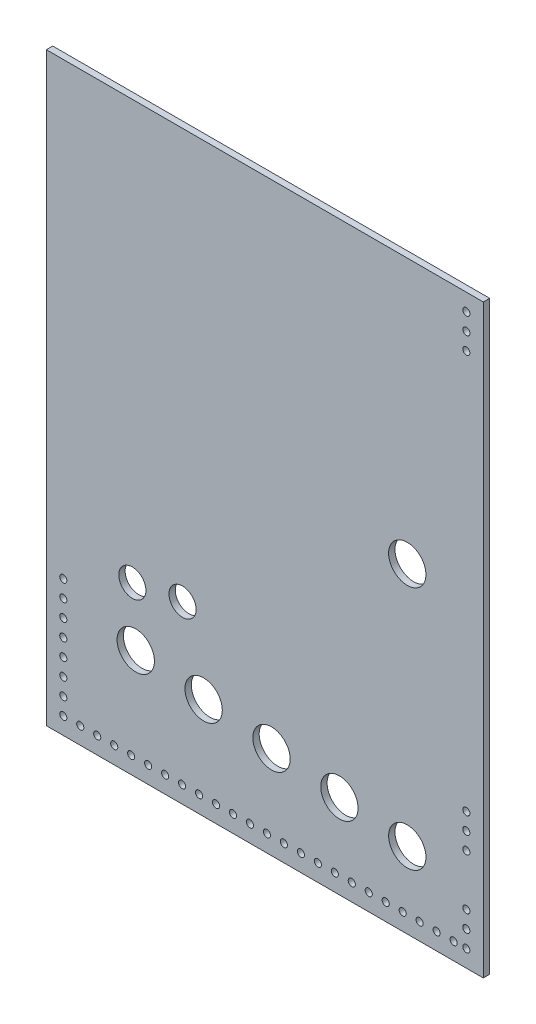
SolidWorks part; units mm, degrees
material "Polypropylene"
ref_plane "Front Plane" through (0, 0, 0) normal (0, 0, 1) x (1, 0, 0)
ref_plane "Top Plane" through (0, 0, 0) normal (0, 1, 0) x (1, 0, 0)
ref_plane "Right Plane" through (0, 0, 0) normal (1, 0, 0) x (0, 0, -1)
sketch "Sketch1" plane through (0, 0, 0) normal (0, 0, 1) x (1, 0, 0)
  line L0 (270.1144, -382.3444) -> (270.1144, -198.1944) construction
  line L1 (0, 0) -> (327.025, 0)
  line L2 (0, 0) -> (0, -438.15)
  line L3 (0, -438.15) -> (327.025, -438.15)
  line L4 (327.025, 0) -> (327.025, -438.15)
  circle A4 centre (270.1144, -198.1944) radius 13.97
  circle A5 centre (101.9257, -306.8134) radius 10.16
  circle A6 centre (64.3744, -313.2564) radius 10.16
  dimension "D4" = 27.94
  dimension "D5" = 20.32
  dimension "D6" = 20.32
  dimension "D1" = 438.15
  dimension "D2" = 327.025
  dimension "D3" = 184.15
extrude "Boss-Extrude1" add sketch "Sketch1" along normal blind 4.7625
sketch "Sketch2" plane through (0, 0, 4.7625) normal (0, 0, 1) x (1, 0, 0)
  circle A1 centre (66.9144, -355.9045) radius 13.97
  dimension "D1" = 27.94
extrude "Cut-Extrude1" cut sketch "Sketch2" against normal up to surface (4.7625 mm away) up to face at (163.5125, -219.075, 0)
sketch "Sketch3" plane through (0, 0, 4.7625) normal (0, 0, 1) x (1, 0, 0)
  line L0 (66.9144, -355.9045) -> (327.025, -355.9045) construction
  line L1 (327.025, -438.15) -> (327.025, 0) construction
  line L2 (66.9144, -355.9045) -> (117.7144, -355.9045) construction
  line L3 (117.7144, -355.9045) -> (168.5144, -355.9045) construction
  line L4 (168.5144, -355.9045) -> (219.3144, -355.9045) construction
  line L5 (219.3144, -355.9045) -> (270.1144, -355.9045) construction
  line L6 (117.7144, -355.9045) -> (117.7144, -362.2545) construction
  line L7 (168.5144, -355.9045) -> (168.5144, -368.6045) construction
  line L8 (219.3144, -355.9045) -> (219.3144, -374.9545) construction
  line L9 (270.1144, -355.9045) -> (270.1144, -381.3045) construction
  line L10 (117.7144, -355.9045) -> (117.7144, -362.2545) construction
  circle A0 centre (117.7144, -362.2545) radius 13.97
  circle A1 centre (168.5144, -368.6045) radius 13.97
  circle A2 centre (219.3144, -374.9545) radius 13.97
  circle A3 centre (270.1144, -381.3045) radius 13.97
  dimension "D8" = 27.94
  dimension "D9" = 27.94
  dimension "D10" = 27.94
  dimension "D11" = 27.94
  dimension "D1" = 50.8
  dimension "D2" = 50.8
  dimension "D3" = 50.8
  dimension "D4" = 50.8
  dimension "D5" = 12.7
  dimension "D6" = 19.05
  dimension "D7" = 25.4
  dimension "D12" = 6.35
extrude "Cut-Extrude2" cut sketch "Sketch3" against normal up to surface (4.7625 mm away) contours A0 | A1 | A2 | A3 up to face at (80.8844, -355.9045, 0)
sketch "Sketch4" plane through (0, 0, 0) normal (0, 0, -1) x (-1, 0, 0)
  line L0 (-12.7, -438.15) -> (-12.7, -425.45) construction
  line L1 (0, -438.15) -> (-327.025, -438.15) construction
  line L2 (-12.7, -425.45) -> (0, -425.45) construction
  line L3 (0, 0) -> (0, -438.15) construction
  line L4 (-327.025, -425.45) -> (0, -425.45) construction
  line L5 (-327.025, 0) -> (0, 0) construction
  line L6 (-163.5125, 0) -> (-163.5125, -438.15) construction
  line L7 (-327.025, -438.15) -> (-327.025, 0) construction
  line L8 (-314.325, -438.15) -> (-314.325, -425.45) construction
  line L9 (-314.325, 0) -> (-314.325, -12.7) construction
  circle A0 centre (-12.7, -425.45) radius 2.667
  circle A1 centre (-12.7, -412.75) radius 2.667
  circle A2 centre (-12.7, -400.05) radius 2.667
  circle A3 centre (-12.7, -387.35) radius 2.667
  circle A4 centre (-12.7, -374.65) radius 2.667
  circle A5 centre (-12.7, -361.95) radius 2.667
  circle A6 centre (-12.7, -349.25) radius 2.667
  circle A7 centre (-12.7, -336.55) radius 2.667
  circle A33 centre (-314.325, -361.95) radius 2.667
  circle A34 centre (-314.325, -349.25) radius 2.667
  circle A35 centre (-314.325, -336.55) radius 2.667
  circle A38 centre (-314.325, -400.05) radius 2.667
  circle A39 centre (-314.325, -412.75) radius 2.667
  circle A40 centre (-314.325, -425.45) radius 2.667
  circle A44 centre (-12.7, -57.15) radius 2.667 [skipped]
  circle A45 centre (-12.7, -69.85) radius 2.667 [skipped]
  circle A46 centre (-12.7, -82.55) radius 2.667 [skipped]
  circle A47 centre (-12.7, -95.25) radius 2.667 [skipped]
  circle A48 centre (-12.7, -107.95) radius 2.667 [skipped]
  circle A49 centre (-12.7, -120.65) radius 2.667 [skipped]
  circle A50 centre (-12.7, -133.35) radius 2.667 [skipped]
  circle A51 centre (-12.7, -146.05) radius 2.667 [skipped]
  circle A52 centre (-12.7, -184.15) radius 2.667 [skipped]
  circle A53 centre (-12.7, -171.45) radius 2.667 [skipped]
  circle A54 centre (-12.7, -158.75) radius 2.667 [skipped]
  circle A55 centre (-12.7, -285.75) radius 2.667 [skipped]
  circle A56 centre (-12.7, -273.05) radius 2.667 [skipped]
  circle A57 centre (-12.7, -260.35) radius 2.667 [skipped]
  circle A58 centre (-12.7, -247.65) radius 2.667 [skipped]
  circle A59 centre (-12.7, -234.95) radius 2.667 [skipped]
  circle A60 centre (-12.7, -222.25) radius 2.667 [skipped]
  circle A61 centre (-12.7, -209.55) radius 2.667 [skipped]
  circle A62 centre (-12.7, -196.85) radius 2.667 [skipped]
  circle A63 centre (-12.7, -323.85) radius 2.667 [skipped]
  circle A64 centre (-12.7, -311.15) radius 2.667 [skipped]
  circle A65 centre (-12.7, -298.45) radius 2.667 [skipped]
  circle A66 centre (-25.4, -425.45) radius 2.667
  circle A67 centre (-38.1, -425.45) radius 2.667
  circle A68 centre (-50.8, -425.45) radius 2.667
  circle A69 centre (-63.5, -425.45) radius 2.667
  circle A70 centre (-76.2, -425.45) radius 2.667
  circle A71 centre (-88.9, -425.45) radius 2.667
  circle A72 centre (-101.6, -425.45) radius 2.667
  circle A73 centre (-114.3, -425.45) radius 2.667
  circle A74 centre (-127, -425.45) radius 2.667
  circle A75 centre (-139.7, -425.45) radius 2.667
  circle A76 centre (-152.4, -425.45) radius 2.667
  circle A77 centre (-165.1, -425.45) radius 2.667
  circle A78 centre (-177.8, -425.45) radius 2.667
  circle A79 centre (-190.5, -425.45) radius 2.667
  circle A80 centre (-203.2, -425.45) radius 2.667
  circle A81 centre (-215.9, -425.45) radius 2.667
  circle A82 centre (-228.6, -425.45) radius 2.667
  circle A83 centre (-241.3, -425.45) radius 2.667
  circle A84 centre (-254, -425.45) radius 2.667
  circle A85 centre (-266.7, -425.45) radius 2.667
  circle A86 centre (-279.4, -425.45) radius 2.667
  circle A87 centre (-292.1, -425.45) radius 2.667
  circle A88 centre (-304.8, -425.45) radius 2.667
  circle A89 centre (-12.7, -19.05) radius 2.667 [skipped]
  circle A90 centre (-12.7, -31.75) radius 2.667 [skipped]
  circle A91 centre (-12.7, -44.45) radius 2.667 [skipped]
  circle A92 centre (-314.325, -12.7) radius 2.667
  circle A93 centre (-314.325, -25.4) radius 2.667
  circle A94 centre (-314.325, -38.1) radius 2.667
  dimension "D3" = 5.334
  dimension "D8" = 5.334
  dimension "D1" = 12.7
  dimension "D2" = 12.7
  dimension "D4" = 24
  dimension "D6" = 12.7
  dimension "D5" = 33
  dimension "D7" = 3
extrude "Cut-Extrude3" cut sketch "Sketch4" against normal through all
